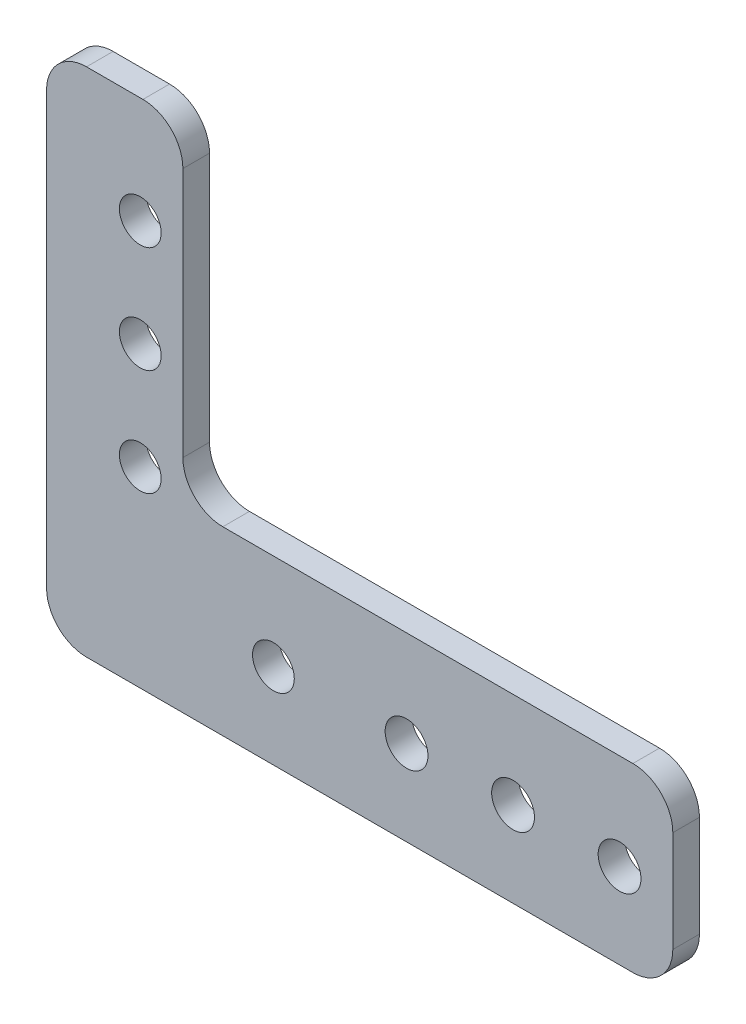
SolidWorks part; units mm, degrees
material "6061-T6 (SS)"
ref_plane "Front Plane" through (0, 0, 0) normal (0, 0, 1) x (1, 0, 0)
ref_plane "Top Plane" through (0, 0, 0) normal (0, 1, 0) x (1, 0, 0)
ref_plane "Right Plane" through (0, 0, 0) normal (1, 0, 0) x (0, 0, -1)
sketch "Sketch1" plane through (0, 0, 0) normal (0, 0, 1) x (1, 0, 0)
  line L1 (-41.275, -31.75) -> (41.275, -31.75)
  line L2 (-41.275, -31.75) -> (-41.275, 31.75)
  line L3 (-41.275, 31.75) -> (41.275, 31.75)
  line L4 (41.275, -31.75) -> (41.275, 31.75)
  line L5 (-41.275, -31.75) -> (41.275, 31.75) construction
  line L6 (-41.275, 31.75) -> (41.275, -31.75) construction
  line L7 (41.275, 31.75) -> (-17.145, 31.75)
  line L8 (41.275, 31.75) -> (41.275, -7.62)
  line L9 (41.275, -7.62) -> (-17.145, -7.62)
  line L10 (-17.145, 31.75) -> (-17.145, -7.62)
  line L11 (-41.275, -31.75) -> (-33.401, -31.75)
  line L12 (-41.275, -31.75) -> (-41.275, 31.75)
  line L13 (-41.275, 31.75) -> (-33.401, 31.75)
  line L14 (-33.401, -31.75) -> (-33.401, 31.75)
  line L15 (-33.401, -31.75) -> (41.275, -31.75)
  line L16 (-33.401, -31.75) -> (-33.401, -29.21)
  line L17 (-33.401, -29.21) -> (41.275, -29.21)
  line L18 (41.275, -31.75) -> (41.275, -29.21)
  circle A0 centre (-22.225, -19.05) radius 2.4892
  circle A1 centre (-22.225, -6.35) radius 2.4892
  circle A2 centre (-22.225, 6.35) radius 2.4892
  circle A3 centre (-22.225, 19.05) radius 2.4892
  circle A4 centre (-6.35, -19.05) radius 2.4892
  circle A5 centre (9.525, -19.05) radius 2.5527
  circle A6 centre (22.225, -19.05) radius 2.5527
  circle A7 centre (34.925, -19.05) radius 2.5527
  point P0 (0, 0)
  point P31 (0, 0)
  dimension "D7" = 4.9784
  dimension "D17" = 12.7
  dimension "D18" = 5.1054
  dimension "D1" = 82.55
  dimension "D2" = 63.5
  dimension "D3" = 24.13
  dimension "D4" = 24.13
  dimension "D5" = 7.874
  dimension "D6" = 63.5
  dimension "D8" = 19.05
  dimension "D9" = 12.7
  dimension "D10" = 12.7
  dimension "D11" = 12.7
  dimension "D12" = 12.7
  dimension "D13" = 12.7
  dimension "D14" = 27.051
  dimension "D15" = 15.875
  dimension "D16" = 2.54
extrude "Boss-Extrude1" add sketch "Sketch1" along normal blind 3.175 contours L14 L17 L4 L9 L10 L3 A6 A5 A4 A3 A2 A1 A0 | A0 region at (-4.4605, -9.7574, 0) region at (-22.225, -19.05, 0)
fillet "Fillet1" radius 4.7625 6 edges at (-33.401, 31.75, 1.5875) (-17.145, 31.75, 1.5875) (-17.145, -7.62, 1.5875) (41.275, -7.62, 1.5875) (41.275, -29.21, 1.5875) (-33.401, -29.21, 1.5875)
